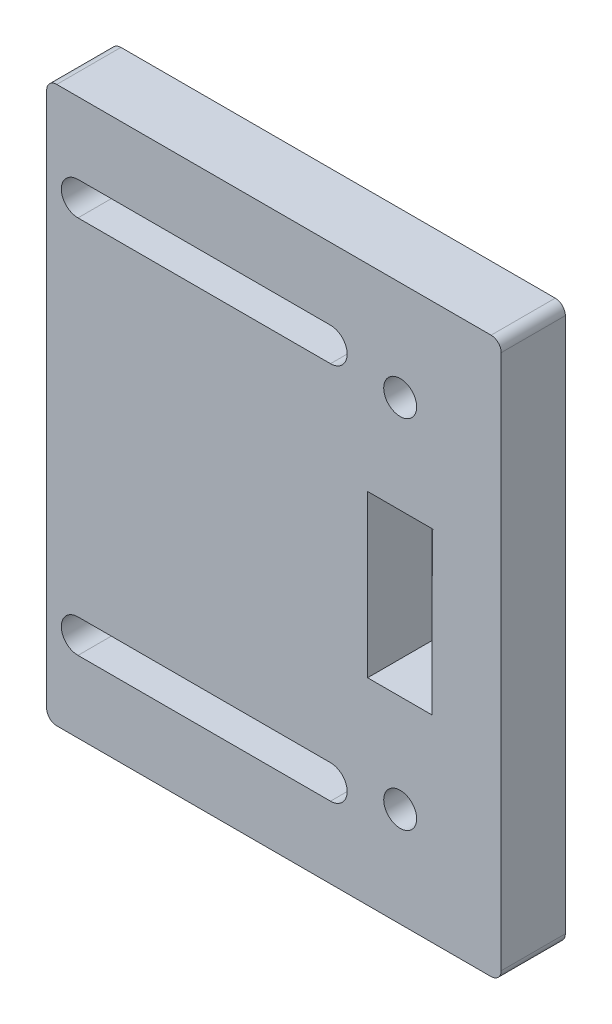
SolidWorks part; units mm, degrees
ref_plane "Front Plane" through (0, 0, 0) normal (0, 0, 1) x (1, 0, 0)
ref_plane "Top Plane" through (0, 0, 0) normal (0, 1, 0) x (1, 0, 0)
ref_plane "Right Plane" through (0, 0, 0) normal (1, 0, 0) x (0, 0, -1)
sketch "Sketch1" plane through (0, 0, 0) normal (0, 0, 1) x (1, 0, 0)
  line L0 (70, -110) -> (70, -90.31) construction
  line L1 (0, 0) -> (90, 0)
  line L2 (0, 0) -> (0, -110)
  line L3 (0, -110) -> (90, -110)
  line L4 (90, 0) -> (90, -110)
  line L6 (70, -39.0256) -> (76.45, -39.0256)
  line L8 (76.25, -70.9756) -> (70, -70.9756)
  line L9 (70, -70.9756) -> (63.55, -70.9756)
  line L10 (63.55, -70.9756) -> (63.55, -39.0256)
  line L11 (63.55, -39.0256) -> (70, -39.0256)
  line L12 (80, 0) -> (80, -19.69) construction
  line L14 (76.45, -39.0256) -> (76.25, -55)
  line L15 (76.25, -55) -> (76.25, -70.9756)
  dimension "D6" = 10
  dimension "D1" = 110
  dimension "D2" = 31.95
  dimension "D3" = 12.9
  dimension "D4" = 19.69
  dimension "D5" = 19.69
  dimension "D7" = 15.9744
  dimension "D8" = 80
extrude "Boss-Extrude2" add sketch "Sketch1" along normal blind 12.7
sketch "Sketch8" plane through (0, 0, 0) normal (0, 0, -1) x (-1, 0, 0)
  line L1 (-70, -110) -> (-70, -90.31) construction
  dimension "D1" = 19.69
  dimension "D2" = 20
hole_wizard "CSK for 1/4 Flat Head Machine Screw3" positions "Sketch9" profile "Sketch10" countersink size "1/4" standard "ANSI Inch" end condition through all
sketch "Sketch9" plane through (0, 0, 0) normal (0, 0, -1) x (-1, 0, 0)
  point P0 (-70, -90.31)
sketch "Sketch10" plane through (70, -90.31, 0) normal (1, 0, 0) x (0, 1, 0)
  line L0 (0, 0) -> (0, 12.7)
  line L1 (0, 12.7) -> (3.2639, 12.7)
  line L2 (3.2639, 12.7) -> (3.2639, 3.6524)
  line L3 (3.2639, 3.6524) -> (6.4389, 0)
  line L5 (6.4389, 0) -> (0, 0)
  line L6 (-3.2639, 3.6524) -> (-6.4389, 0) construction
  line L11 (0, -6.35) -> (0, 107.95) construction
  dimension "Thru Hole Dia." = 6.5278
  dimension "Thru Hole Depth" = 12.7
  dimension "Near C'Sink Dia." = 12.8778
  dimension "Near C'Sink Angle" = 82
sketch "Sketch11" plane through (0, 0, 0) normal (0, 0, -1) x (-1, 0, 0)
  line L0 (-70, 0) -> (-70, -19.69)
  dimension "D1" = 19.69
  dimension "D2" = 20
hole_wizard "CSK for 1/4 Flat Head Machine Screw4" positions "Sketch12" profile "Sketch13" countersink size "1/4" standard "ANSI Inch" end condition through all
sketch "Sketch12" plane through (0, 0, 0) normal (0, 0, -1) x (-1, 0, 0)
  point P0 (-70, -19.69)
sketch "Sketch13" plane through (70, -19.69, 0) normal (1, 0, 0) x (0, 1, 0)
  line L0 (0, 0) -> (0, 12.7)
  line L1 (0, 12.7) -> (3.2639, 12.7)
  line L2 (3.2639, 12.7) -> (3.2639, 3.6524)
  line L3 (3.2639, 3.6524) -> (6.4389, 0)
  line L5 (6.4389, 0) -> (0, 0)
  line L6 (-3.2639, 3.6524) -> (-6.4389, 0) construction
  line L11 (0, -6.35) -> (0, 107.95) construction
  dimension "Thru Hole Dia." = 6.5278
  dimension "Thru Hole Depth" = 12.7
  dimension "Near C'Sink Dia." = 12.8778
  dimension "Near C'Sink Angle" = 82
fillet "Fillet1" radius 2 4 edges at (0, 0, 6.35) (90, 0, 6.35) (0, -110, 6.35) (90, -110, 6.35)
sketch "Sketch15" plane through (0, 0, 0) normal (0, 0, -1) x (-1, 0, 0)
  line L0 (-56.2003, -14.19) -> (-6.2003, -14.19)
  line L1 (-56.2003, -20.79) -> (-6.2003, -20.79)
  line L2 (0, -55) -> (-82.6046, -55) construction
  line L3 (0, -2) -> (0, -108) construction
  line L4 (-56.2003, -89.21) -> (-6.2003, -89.21)
  line L5 (-56.2003, -95.81) -> (-6.2003, -95.81)
  arc A0 (-6.2003, -14.19) -> (-6.2003, -20.79) centre (-6.2003, -17.49) cw
  arc A1 (-56.2003, -20.79) -> (-56.2003, -14.19) centre (-56.2003, -17.49) cw
  arc A2 (-6.2003, -95.81) -> (-6.2003, -89.21) centre (-6.2003, -92.51) ccw
  arc A3 (-56.2003, -89.21) -> (-56.2003, -95.81) centre (-56.2003, -92.51) ccw
  dimension "D3" = 3.3
  dimension "D4" = 68.42
  dimension "D1" = 50
  dimension "D2" = 50
extrude "Cut-Extrude1" cut sketch "Sketch15" against normal through all
